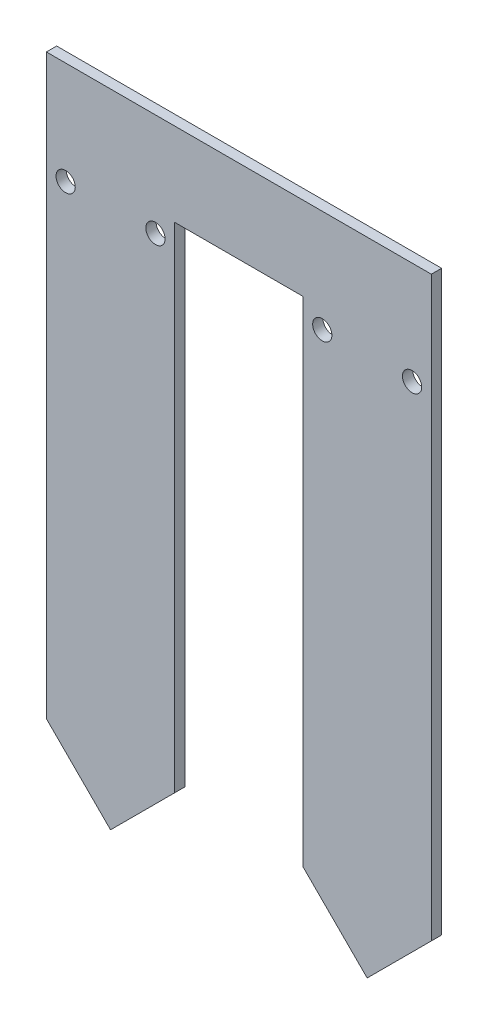
SolidWorks part; units mm, degrees
ref_plane "Ön Düzlem" through (0, 0, 0) normal (0, 0, 1) x (1, 0, 0)
ref_plane "Üst Düzlem" through (0, 0, 0) normal (0, 1, 0) x (1, 0, 0)
ref_plane "Sağ Düzlem" through (0, 0, 0) normal (1, 0, 0) x (0, 0, -1)
sketch "Çizim1" plane through (0, 0, 0) normal (0, 0, 1) x (1, 0, 0)
  line L0 (0, -55) -> (-10, -45)
  line L1 (-10, 45) -> (10, 45)
  line L2 (-10, 45) -> (-10, -45)
  line L4 (10, 32) -> (10, -45)
  line L5 (0, -55) -> (10, -45)
  line L6 (10, 32) -> (30, 32)
  line L7 (30, 32) -> (30, -45)
  line L8 (30, -45) -> (40, -55)
  line L9 (40, -55) -> (50, -45)
  line L10 (50, -45) -> (50, 45)
  line L11 (10, 45) -> (50, 45)
  circle A0 centre (-7, 29) radius 1.5
  circle A1 centre (7, 29) radius 1.5
  circle A2 centre (33, 29) radius 1.5
  circle A3 centre (47, 29) radius 1.5
  point P4 (0, 45)
  point P6 (-10, 0)
  point P22 (0, 0)
  dimension "D3" = 3
  dimension "D4" = 3
  dimension "D1" = 90
  dimension "D2" = 20
  dimension "D5" = 84
  dimension "D6" = 3
  dimension "D7" = 3
  dimension "D8" = 10
  dimension "D9" = 90
  dimension "D10" = 20
  dimension "D11" = 20
  dimension "D12" = 90
  dimension "D13" = 10
  dimension "D14" = 3
  dimension "D15" = 3
extrude "Yükseklik-Ekstrüzyon1" add sketch "Çizim1" along normal blind 1.6
